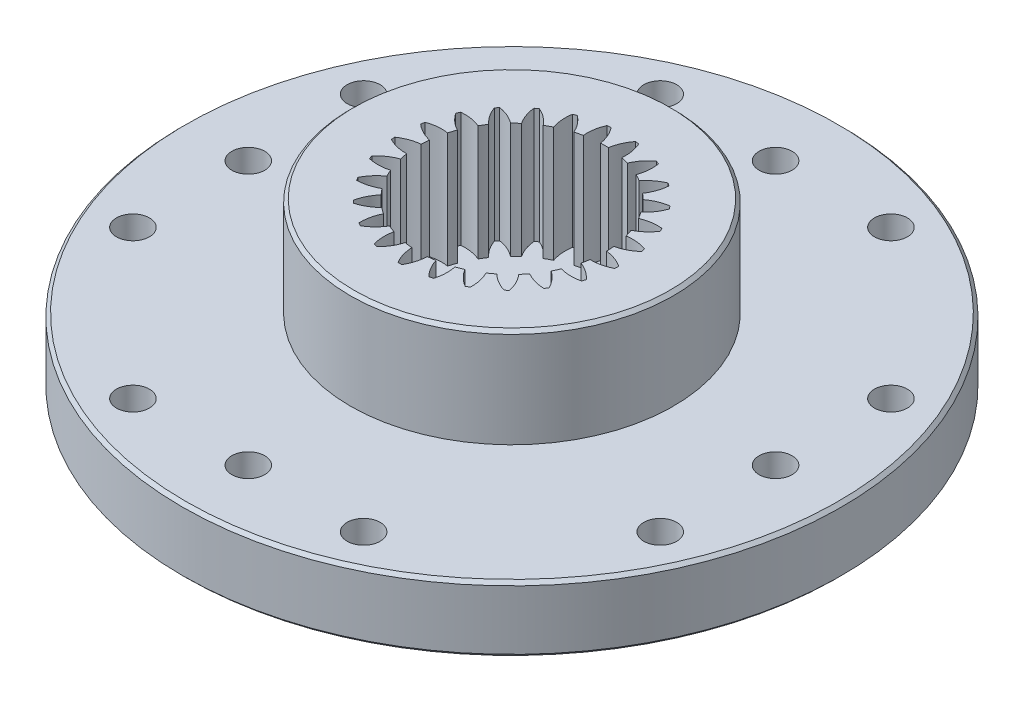
SolidWorks part; units mm, degrees
note: The reader was unsure of these and kept them because the rebuilt part matched: shared geometry of "ｽｹｯﾁ4<3>", "ｽｹｯﾁ4<4>".
material "ABS"
ref_plane "正面" through (0, 0, 0) normal (0, 0, 1) x (1, 0, 0)
ref_plane "平面" through (0, 0, 0) normal (0, 1, 0) x (1, 0, 0)
ref_plane "右側面" through (0, 0, 0) normal (1, 0, 0) x (0, 0, -1)
sketch "ｽｹｯﾁ1" plane through (0, 0, 0) normal (0, 1, 0) x (1, 0, 0)
  circle A0 centre (0, 0) radius 10
extrude "ﾎﾞｽ - 押し出し1" add sketch "ｽｹｯﾁ1" along normal blind 2
sketch "ｽｹｯﾁ2" plane through (0, 2, 0) normal (0, 1, 0) x (1, 0, 0)
  circle A0 centre (0, 0) radius 4.9
extrude "ﾎﾞｽ - 押し出し2" add sketch "ｽｹｯﾁ2" along normal blind 3
sketch "ｽｹｯﾁ3" plane through (0, 0, 0) normal (0, -1, 0) x (1, 0, 0)
  line L0 (0, 8) -> (-3.5, 8) construction
  line L1 (0, 0) -> (0, 8) construction
  line L2 (0, 8) -> (3.5, 8) construction
  circle A0 centre (-3.5, 8) radius 0.5
  circle A1 centre (0, 8) radius 0.5
  circle A2 centre (3.5, 8) radius 0.5
  circle A3 centre (8, 0) radius 0.5
  circle A4 centre (8, 3.5) radius 0.5
  circle A5 centre (8, -3.5) radius 0.5
  circle A6 centre (0, -8) radius 0.5
  circle A7 centre (3.5, -8) radius 0.5
  circle A8 centre (-3.5, -8) radius 0.5
  circle A9 centre (-8, 0) radius 0.5
  circle A10 centre (-8, -3.5) radius 0.5
  circle A11 centre (-8, 3.5) radius 0.5
  point P29 (0, 0)
  dimension "D1" = 4
extrude "ｶｯﾄ - 押し出し1" cut sketch "ｽｹｯﾁ3" against normal blind 3
sketch "ｽｹｯﾁ4" plane through (0, 0, 0) normal (0, -1, 0) x (1, 0, 0)
  circle A0 centre (0, 0) radius 4.35
  circle A1 centre (0, 0) radius 2.9
  circle A2 centre (0, 0) radius 1.4
extrude "ｶｯﾄ - 押し出し2" cut sketch "ｽｹｯﾁ4" against normal through all contours A2
extrude "ｶｯﾄ - 押し出し3" cut sketch "ｽｹｯﾁ4<3>" against normal blind 0.45 contours A0 A1
sketch "ｽｹｯﾁ4<3>" plane through (0, 0, 0) normal (0, -1, 0) x (1, 0, 0) same geometry as "ｽｹｯﾁ4"
extrude "ｶｯﾄ - 押し出し4" cut sketch "ｽｹｯﾁ4<4>" against normal blind 0.95 contours A1 A2
sketch "ｽｹｯﾁ4<4>" plane through (0, 0, 0) normal (0, -1, 0) x (1, 0, 0) same geometry as "ｽｹｯﾁ4"
sketch "ｽｹｯﾁ6" plane through (0, 5, 0) normal (0, 1, 0) x (1, 0, 0)
  line L3 (-0.2102, 3.1179) -> (-0.391, 3.0951) construction
  arc A0 (0.1175, 2.809) -> (-0.1175, 2.809) centre (0, 0) ccw
  arc A1 (0.3689, 3.3803) -> (-0.3689, 3.3803) centre (0, 0) ccw
  circle A2 centre (0, 0) radius 3.125 construction
  circle A3 centre (0, 0) radius 2.9365 construction
  arc A4 (-0.1175, 2.809) -> (-0.3689, 3.3803) centre (-1.3511, 2.6072) ccw
  arc A5 (0.3689, 3.3803) -> (0.1175, 2.809) centre (1.3511, 2.6072) ccw
  arc A6 (1.1979, 3.1824) -> (0.8124, 2.6916) centre (1.9571, 2.1893) ccw
  arc A7 (0.8124, 2.6916) -> (0.5847, 2.75) centre (0, 0) ccw
  arc A8 (0.5847, 2.75) -> (0.4834, 3.3659) centre (-0.6603, 2.8613) ccw
  arc A9 (1.1979, 3.1824) -> (0.4834, 3.3659) centre (0, 0) ccw
  arc A10 (1.9517, 2.7845) -> (1.4563, 2.405) centre (2.4401, 1.6338) ccw
  arc A11 (1.4563, 2.405) -> (1.2503, 2.5182) centre (0, 0) ccw
  arc A12 (1.2503, 2.5182) -> (1.3052, 3.1399) centre (0.072, 2.9357) ccw
  arc A13 (1.9517, 2.7845) -> (1.3052, 3.1399) centre (0, 0) ccw
  arc A14 (2.5829, 2.2116) -> (2.0086, 1.9672) centre (2.7697, 0.9757) ccw
  arc A15 (2.0086, 1.9672) -> (1.8372, 2.1282) centre (0, 0) ccw
  arc A16 (1.8372, 2.1282) -> (2.0451, 2.7167) centre (0.7998, 2.8255) ccw
  arc A17 (2.5829, 2.2116) -> (2.0451, 2.7167) centre (0, 0) ccw
  arc A18 (3.0518, 1.4998) -> (2.4347, 1.4059) centre (2.9253, 0.2562) ccw
  arc A19 (2.4347, 1.4059) -> (2.3088, 1.6044) centre (0, 0) ccw
  arc A20 (2.3088, 1.6044) -> (2.6565, 2.1227) centre (1.4774, 2.5378) ccw
  arc A21 (3.0518, 1.4998) -> (2.6565, 2.1227) centre (0, 0) ccw
  arc A22 (3.3289, 0.6938) -> (2.7079, 0.7563) centre (2.8972, -0.4793) ccw
  arc A23 (2.7079, 0.7563) -> (2.6352, 0.9798) centre (0, 0) ccw
  arc A24 (2.6352, 0.9798) -> (3.1009, 1.3954) centre (2.0621, 2.0907) ccw
  arc A25 (3.3289, 0.6938) -> (3.1009, 1.3954) centre (0, 0) ccw
  arc A26 (3.3968, -0.1559) -> (2.8109, 0.0591) centre (2.6869, -1.1848) ccw
  arc A27 (2.8109, 0.0591) -> (2.7961, 0.2937) centre (0, 0) ccw
  arc A28 (2.7961, 0.2937) -> (3.3505, 0.5804) centre (2.5173, 1.5122) ccw
  arc A29 (3.3968, -0.1559) -> (3.3505, 0.5804) centre (0, 0) ccw
  arc A30 (3.2513, -0.9958) -> (2.7373, -0.6418) centre (2.3079, -1.8158) ccw
  arc A31 (2.7373, -0.6418) -> (2.7813, -0.4109) centre (0, 0) ccw
  arc A32 (2.7813, -0.4109) -> (3.3896, -0.2711) centre (2.8142, 0.8387) ccw
  arc A33 (3.2513, -0.9958) -> (3.3896, -0.2711) centre (0, 0) ccw
  arc A34 (2.9016, -1.7731) -> (2.4917, -1.3024) centre (1.7838, -2.3327) ccw
  arc A35 (2.4917, -1.3024) -> (2.5917, -1.0897) centre (0, 0) ccw
  arc A36 (2.5917, -1.0897) -> (3.2157, -1.1055) centre (2.9344, 0.1124) ccw
  arc A37 (2.9016, -1.7731) -> (3.2157, -1.1055) centre (0, 0) ccw
  arc A38 (2.3695, -2.4389) -> (2.0895, -1.8811) centre (1.1477, -2.703) ccw
  arc A39 (2.0895, -1.8811) -> (2.2393, -1.7) centre (0, 0) ccw
  arc A40 (2.2393, -1.7) -> (2.8397, -1.8705) centre (2.8702, -0.6208) ccw
  arc A41 (2.3695, -2.4389) -> (2.8397, -1.8705) centre (0, 0) ccw
  arc A42 (1.6885, -2.9516) -> (1.556, -2.3416) centre (0.4394, -2.9035) ccw
  arc A43 (1.556, -2.3416) -> (1.7462, -2.2035) centre (0, 0) ccw
  arc A44 (1.7462, -2.2035) -> (2.2853, -2.5179) centre (2.6256, -1.3151) ccw
  arc A45 (1.6885, -2.9516) -> (2.2853, -2.5179) centre (0, 0) ccw
  arc A46 (0.9014, -3.2787) -> (0.9248, -2.655) centre (-0.2965, -2.9215) ccw
  arc A47 (0.9248, -2.655) -> (1.1434, -2.5685) centre (0, 0) ccw
  arc A48 (1.1434, -2.5685) -> (1.5874, -3.0072) centre (2.216, -1.9268) ccw
  arc A49 (0.9014, -3.2787) -> (1.5874, -3.0072) centre (0, 0) ccw
  arc A50 (0.0577, -3.3999) -> (0.2355, -2.8016) centre (-1.0137, -2.756) ccw
  arc A51 (0.2355, -2.8016) -> (0.4687, -2.7722) centre (0, 0) ccw
  arc A52 (0.4687, -2.7722) -> (0.7896, -3.3074) centre (1.6673, -2.4173) ccw
  arc A53 (0.0577, -3.3999) -> (0.7896, -3.3074) centre (0, 0) ccw
  arc A54 (-0.7896, -3.3074) -> (-0.4687, -2.7722) centre (-1.6673, -2.4173) ccw
  arc A55 (-0.4687, -2.7722) -> (-0.2355, -2.8016) centre (0, 0) ccw
  arc A56 (-0.2355, -2.8016) -> (-0.0577, -3.3999) centre (1.0137, -2.756) ccw
  arc A57 (-0.7896, -3.3074) -> (-0.0577, -3.3999) centre (0, 0) ccw
  arc A58 (-1.5874, -3.0072) -> (-1.1434, -2.5685) centre (-2.216, -1.9268) ccw
  arc A59 (-1.1434, -2.5685) -> (-0.9248, -2.655) centre (0, 0) ccw
  arc A60 (-0.9248, -2.655) -> (-0.9014, -3.2787) centre (0.2965, -2.9215) ccw
  arc A61 (-1.5874, -3.0072) -> (-0.9014, -3.2787) centre (0, 0) ccw
  arc A62 (-2.2853, -2.5179) -> (-1.7462, -2.2035) centre (-2.6256, -1.3151) ccw
  arc A63 (-1.7462, -2.2035) -> (-1.556, -2.3416) centre (0, 0) ccw
  arc A64 (-1.556, -2.3416) -> (-1.6885, -2.9516) centre (-0.4394, -2.9035) ccw
  arc A65 (-2.2853, -2.5179) -> (-1.6885, -2.9516) centre (0, 0) ccw
  arc A66 (-2.8397, -1.8705) -> (-2.2393, -1.7) centre (-2.8702, -0.6208) ccw
  arc A67 (-2.2393, -1.7) -> (-2.0895, -1.8811) centre (0, 0) ccw
  arc A68 (-2.0895, -1.8811) -> (-2.3695, -2.4389) centre (-1.1477, -2.703) ccw
  arc A69 (-2.8397, -1.8705) -> (-2.3695, -2.4389) centre (0, 0) ccw
  arc A70 (-3.2157, -1.1055) -> (-2.5917, -1.0897) centre (-2.9344, 0.1124) ccw
  arc A71 (-2.5917, -1.0897) -> (-2.4917, -1.3024) centre (0, 0) ccw
  arc A72 (-2.4917, -1.3024) -> (-2.9016, -1.7731) centre (-1.7838, -2.3327) ccw
  arc A73 (-3.2157, -1.1055) -> (-2.9016, -1.7731) centre (0, 0) ccw
  arc A74 (-3.3896, -0.2711) -> (-2.7813, -0.4109) centre (-2.8142, 0.8387) ccw
  arc A75 (-2.7813, -0.4109) -> (-2.7373, -0.6418) centre (0, 0) ccw
  arc A76 (-2.7373, -0.6418) -> (-3.2513, -0.9958) centre (-2.3079, -1.8158) ccw
  arc A77 (-3.3896, -0.2711) -> (-3.2513, -0.9958) centre (0, 0) ccw
  arc A78 (-3.3505, 0.5804) -> (-2.7961, 0.2937) centre (-2.5173, 1.5122) ccw
  arc A79 (-2.7961, 0.2937) -> (-2.8109, 0.0591) centre (0, 0) ccw
  arc A80 (-2.8109, 0.0591) -> (-3.3968, -0.1559) centre (-2.6869, -1.1848) ccw
  arc A81 (-3.3505, 0.5804) -> (-3.3968, -0.1559) centre (0, 0) ccw
  arc A82 (-3.1009, 1.3954) -> (-2.6352, 0.9798) centre (-2.0621, 2.0907) ccw
  arc A83 (-2.6352, 0.9798) -> (-2.7079, 0.7563) centre (0, 0) ccw
  arc A84 (-2.7079, 0.7563) -> (-3.3289, 0.6938) centre (-2.8972, -0.4793) ccw
  arc A85 (-3.1009, 1.3954) -> (-3.3289, 0.6938) centre (0, 0) ccw
  arc A86 (-2.6565, 2.1227) -> (-2.3088, 1.6044) centre (-1.4774, 2.5378) ccw
  arc A87 (-2.3088, 1.6044) -> (-2.4347, 1.4059) centre (0, 0) ccw
  arc A88 (-2.4347, 1.4059) -> (-3.0518, 1.4998) centre (-2.9253, 0.2562) ccw
  arc A89 (-2.6565, 2.1227) -> (-3.0518, 1.4998) centre (0, 0) ccw
  arc A90 (-2.0451, 2.7167) -> (-1.8372, 2.1282) centre (-0.7998, 2.8255) ccw
  arc A91 (-1.8372, 2.1282) -> (-2.0086, 1.9672) centre (0, 0) ccw
  arc A92 (-2.0086, 1.9672) -> (-2.5829, 2.2116) centre (-2.7697, 0.9757) ccw
  arc A93 (-2.0451, 2.7167) -> (-2.5829, 2.2116) centre (0, 0) ccw
  arc A94 (-1.3052, 3.1399) -> (-1.2503, 2.5182) centre (-0.072, 2.9357) ccw
  arc A95 (-1.2503, 2.5182) -> (-1.4563, 2.405) centre (0, 0) ccw
  arc A96 (-1.4563, 2.405) -> (-1.9517, 2.7845) centre (-2.4401, 1.6338) ccw
  arc A97 (-1.3052, 3.1399) -> (-1.9517, 2.7845) centre (0, 0) ccw
  arc A98 (-0.4834, 3.3659) -> (-0.5847, 2.75) centre (0.6603, 2.8613) ccw
  arc A99 (-0.5847, 2.75) -> (-0.8124, 2.6916) centre (0, 0) ccw
  arc A100 (-0.8124, 2.6916) -> (-1.1979, 3.1824) centre (-1.9571, 2.1893) ccw
  arc A101 (-0.4834, 3.3659) -> (-1.1979, 3.1824) centre (0, 0) ccw
  circle A102 centre (0, 0) radius 2.8115
  circle A103 centre (0, 0) radius 3.4004
  point P158 (0, 0)
  dimension "D1" = 25
extrude "ｶｯﾄ - 押し出し5" cut sketch "ｽｹｯﾁ6" against normal blind 3.5
chamfer "面取り1" distance 0.1 angle 45 3 edges at (0, 0, 10) (0, 2, 10) (0, 5, 4.9)
